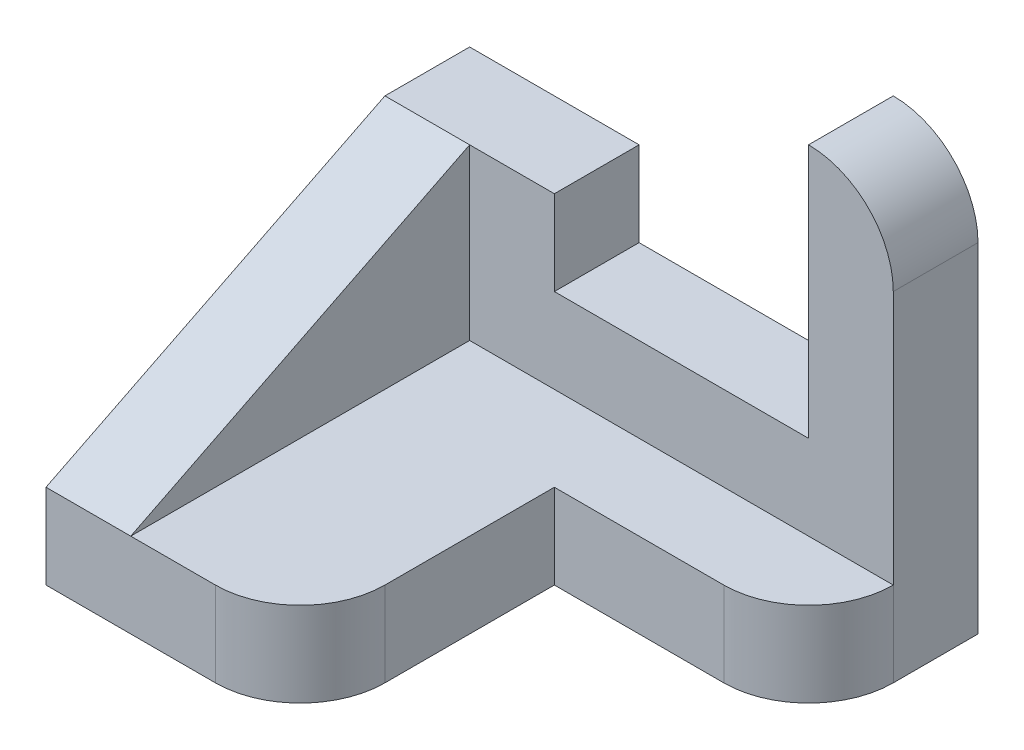
SolidWorks part; units mm, degrees
ref_plane "前基準面" through (0, 0, 0) normal (0, 0, 1) x (1, 0, 0)
ref_plane "上基準面" through (0, 0, 0) normal (0, 1, 0) x (1, 0, 0)
ref_plane "右基準面" through (0, 0, 0) normal (1, 0, 0) x (0, 0, -1)
sketch "草圖1" plane through (0, 0, 0) normal (0, 1, 0) x (1, 0, 0)
  line L0 (0, 0) -> (0, 50)
  line L1 (0, 50) -> (60, 50)
  line L2 (60, 50) -> (60, 40)
  line L3 (50, 30) -> (30, 30)
  line L4 (30, 30) -> (30, 10)
  line L5 (20, 0) -> (0, 0)
  arc A0 (60, 40) -> (50, 30) centre (50, 40) cw
  arc A1 (30, 10) -> (20, 0) centre (20, 10) cw
  dimension "D5" = 10
  dimension "D6" = 10
  dimension "D1" = 60
  dimension "D2" = 50
  dimension "D3" = 20
  dimension "D4" = 30
extrude "填料-伸長1" add sketch "草圖1" along normal blind 10
sketch "草圖2" plane through (0, 0, -50) normal (0, 0, -1) x (-1, 0, 0)
  line L0 (0, 10) -> (0, 30)
  line L1 (0, 30) -> (-20, 30)
  line L2 (-20, 30) -> (-20, 20)
  line L3 (-20, 20) -> (-50, 20)
  line L4 (-50, 20) -> (-50, 50)
  line L5 (-50, 50) -> (-60, 50)
  line L6 (-60, 50) -> (-60, 10)
  line L7 (-60, 10) -> (0, 10) construction
  line L8 (-60, 10) -> (-60, 0) construction
  line L9 (0, 10) -> (-60, 10)
  dimension "D1" = 40
  dimension "D2" = 10
  dimension "D3" = 20
  dimension "D4" = 10
  dimension "D5" = 20
extrude "填料-伸長2" add sketch "草圖2" against normal blind 10
fillet "圓角1" radius 10 1 edges at (60, 50, -45)
sketch "草圖3" plane through (0, 0, 0) normal (-1, 0, 0) x (0, 0, 1)
  line L0 (-40, 30) -> (0, 10)
  line L1 (-40, 10) -> (0, 10) construction
  line L2 (0, 10) -> (0, 0) construction
  line L3 (0, 10) -> (-40, 10)
  line L4 (-40, 10) -> (-40, 30) construction
  line L5 (-40, 10) -> (-40, 30)
extrude "填料-伸長3" add sketch "草圖3" against normal blind 10
